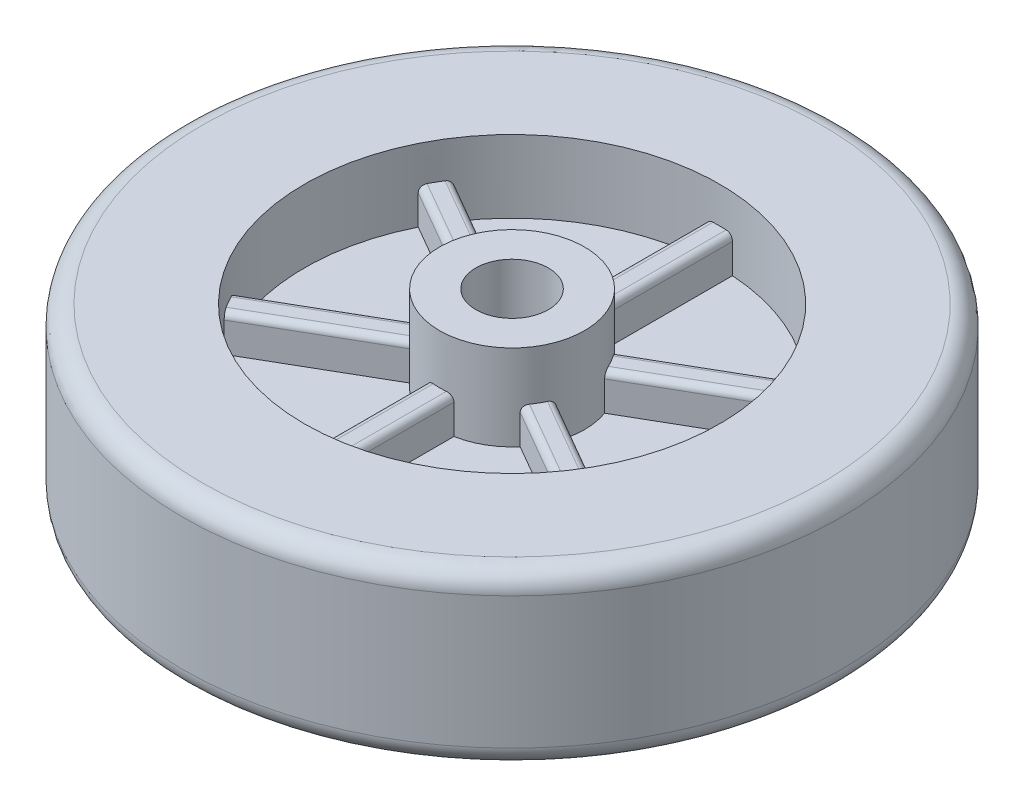
SolidWorks part; units mm, degrees
ref_plane "Front Plane" through (0, 0, 0) normal (0, 0, 1) x (1, 0, 0)
ref_plane "Top Plane" through (0, 0, 0) normal (0, 1, 0) x (1, 0, 0)
ref_plane "Right Plane" through (0, 0, 0) normal (1, 0, 0) x (0, 0, -1)
sketch "Sketch1" plane through (0, 0, 0) normal (0, 1, 0) x (1, 0, 0)
  circle A0 centre (0, 0) radius 50
  circle A1 centre (0, 0) radius 11
  circle A2 centre (0, 0) radius 31.5
  circle A3 centre (0, 0) radius 5.5
  point P7 (0, 0)
  dimension "D1" = 100
  dimension "D2" = 22
  dimension "D3" = 63
  dimension "D4" = 11
extrude "Boss-Extrude1" add sketch "Sketch1" along normal blind 13 and the other way blind 13 contours A0 A2 region at (-48.5858, 0, 0)
extrude "Boss-Extrude2" add sketch "Sketch1<3>" along normal blind 15 and the other way blind 15 separate body contours A1 A3 region at (-10.6889, 0, 0)
sketch "Sketch1<3>" plane through (0, 0, 0) normal (0, 1, 0) x (1, 0, 0) same geometry as "Sketch1"
ref_plane "Plane1" through (0, 0, 0) normal (0, 1, 0) x (1, 0, 0)
sketch "Sketch2" plane through (0, 0, 0) normal (0, 1, 0) x (1, 0, 0)
  line L0 (-2, 31.4364) -> (-2, 10.8167)
  line L1 (2, 31.4364) -> (2, 10.8167)
  line L2 (-2, 10.8167) -> (2, 10.8167) construction
  line L3 (26.2248, 17.4503) -> (8.3675, 7.1404)
  line L4 (28.2248, 13.9862) -> (10.3675, 3.6763)
  line L5 (28.2248, -13.9862) -> (10.3675, -3.6763)
  line L6 (26.2248, -17.4503) -> (8.3675, -7.1404)
  line L7 (2, -31.4364) -> (2, -10.8167)
  line L8 (-2, -31.4364) -> (-2, -10.8167)
  line L9 (-26.2248, -17.4503) -> (-8.3675, -7.1404)
  line L10 (-28.2248, -13.9862) -> (-10.3675, -3.6763)
  line L11 (-28.2248, 13.9862) -> (-10.3675, 3.6763)
  line L12 (-26.2248, 17.4503) -> (-8.3675, 7.1404)
  circle A0 centre (0, 0) radius 31.5
  circle A1 centre (0, 0) radius 31.5 construction
  circle A2 centre (0, 0) radius 11
  circle A4 centre (0, 0) radius 5.5 construction
  point P9 (0, 0)
  point P11 (0, 0)
  dimension "D3" = 22
  dimension "D1" = 4
  dimension "D2" = 6
extrude "Boss-Extrude3" add sketch "Sketch2" along normal blind 7.5 and the other way blind 7.5 contours A2 L1 A0 L0 | A2 L12 A0 L11 | A2 L10 A0 L9 | A2 L8 A0 L7 | A2 L6 A0 L5 | A2 L4 A0 L3 region at (0, 0, -21.2089) region at (-18.3674, 0, -10.6044) region at (18.3674, 0, -10.6044) region at (-18.3674, 0, 10.6044) region at (18.3674, 0, 10.6044) region at (0, 0, 21.2089)
extrude "Boss-Extrude4" add sketch "Sketch2<3>" along normal blind 2 and the other way blind 2 contours A0
sketch "Sketch2<3>" plane through (0, 0, 0) normal (0, 1, 0) x (1, 0, 0) same geometry as "Sketch2"
fillet "Fillet1" radius 1 24 edges at (19.2961, -7.5, -8.8312) (17.2961, -7.5, -12.2953) (2, -7.5, -21.1265) (-2, -7.5, -21.1265) (-17.2961, -7.5, -12.2953) (-19.2961, -7.5, -8.8312) (-19.2961, -7.5, 8.8312) (-17.2961, -7.5, 12.2953) (-2, -7.5, 21.1265) (2, -7.5, 21.1265) (-19.2961, 7.5, 8.8312) (-17.2961, 7.5, 12.2953) (-2, 7.5, 21.1265) (2, 7.5, 21.1265) (17.2961, 7.5, 12.2953) (19.2961, 7.5, 8.8312) (19.2961, 7.5, -8.8312) (17.2961, 7.5, -12.2953) (2, 7.5, -21.1265) (-2, 7.5, -21.1265) (-17.2961, 7.5, -12.2953) (-19.2961, 7.5, -8.8312) (19.2961, -7.5, 8.8312) (17.2961, -7.5, 12.2953)
fillet "Fillet2" radius 3 2 edges at (0, -13, 50) (0, 13, 50)
extrude "Cut-Extrude1" cut sketch "Sketch1<4>" against normal through all both and the other way through all contours A3
sketch "Sketch1<4>" plane through (0, 0, 0) normal (0, 1, 0) x (1, 0, 0) same geometry as "Sketch1"
